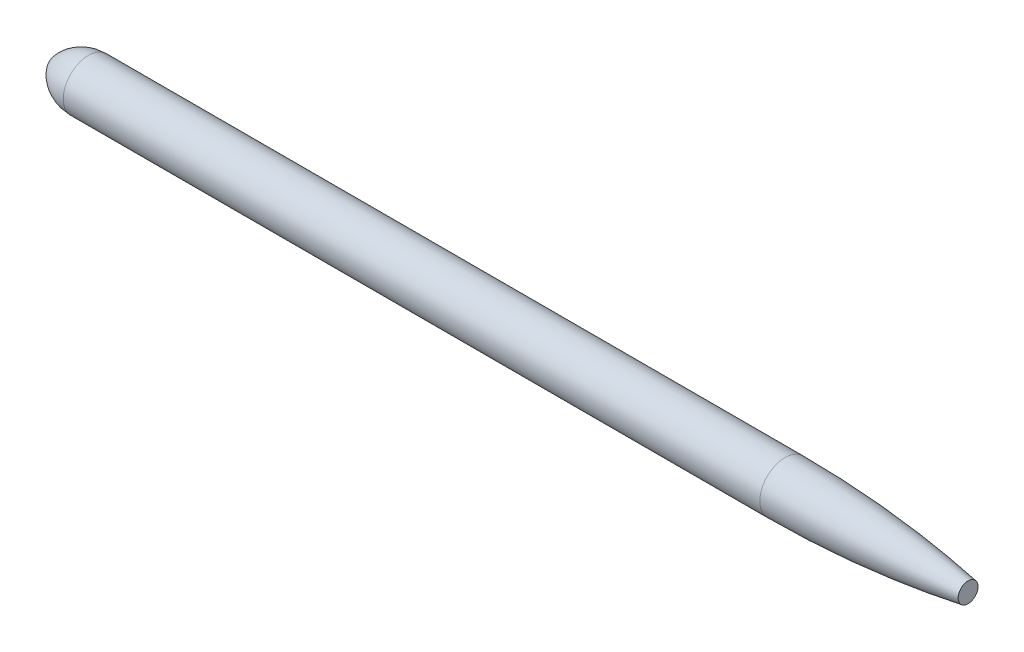
SolidWorks part; units mm, degrees
ref_plane "Front Plane" through (0, 0, 0) normal (0, 0, 1) x (1, 0, 0)
ref_plane "Top Plane" through (0, 0, 0) normal (0, 1, 0) x (1, 0, 0)
ref_plane "Right Plane" through (0, 0, 0) normal (1, 0, 0) x (0, 0, -1)
sketch "rootSketch" plane through (0, 0, 0) normal (0, 1, 0) x (1, 0, 0)
  line L0 (0, 0) -> (12000, 0) construction
  line L1 (270, -177.8) -> (270, 177.8) construction
  line L2 (0, 0) -> (6470, 0)
  line L3 (270, -177.8) -> (5180, -177.8)
  line L4 (6470, -70) -> (6470, 0)
  arc A0 (5180, -177.8) -> (6470, -70) centre (5180, 7594.5601) ccw
  arc A1 (270, -177.8) -> (0, 0) centre (270, 116.1056) cw
  point P5 (270, 0)
  dimension "rootMaxThickness" = 355.6
  dimension "D1" = 6470
  dimension "D2" = 270
  dimension "D3" = 1290
  dimension "D4" = 70
revolve "Revolve1" add sketch "rootSketch" angle 360 about L0
ref_plane "Plane1" through (5330, 0, 0) normal (1, 0, 0) x (0, 0, -1)
equation "\"chord\" = 6.47"
equation "\"NACAairfoil\"= 0006"
equation "\"tailCutoffPercentage\"= 0.18"
equation "\"D1@rootSketch\"=\"chord\""
